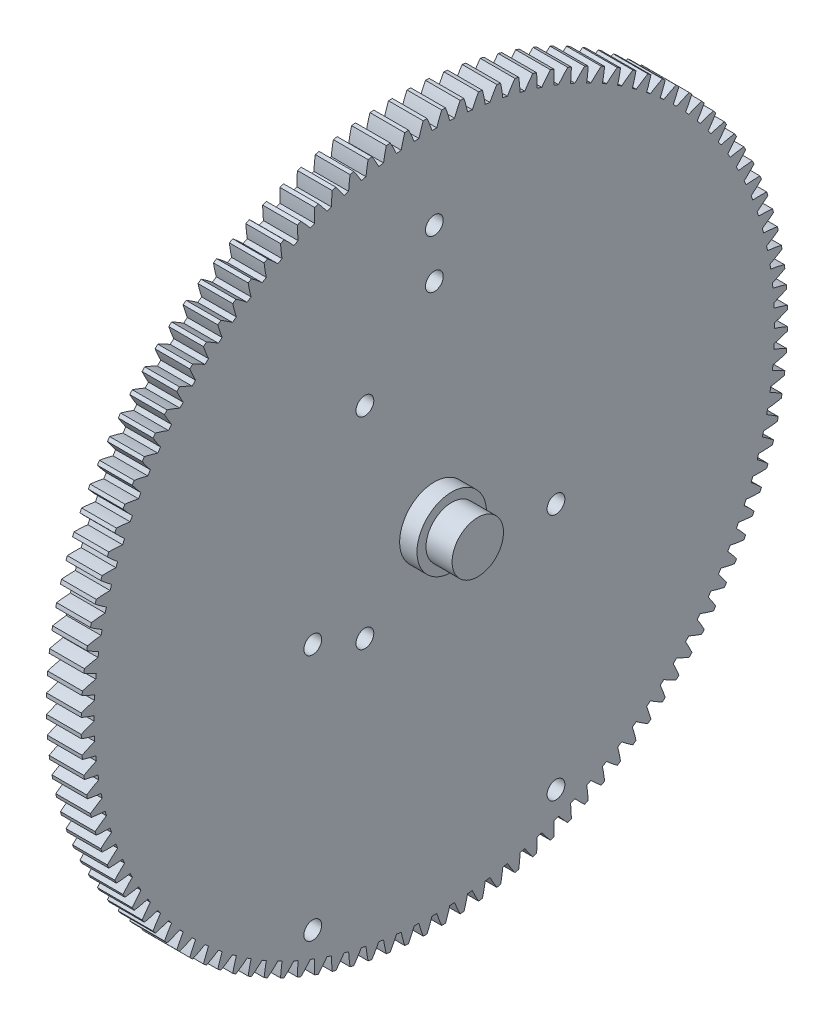
SolidWorks part; units mm, degrees
ref_plane "Plane1" through (0, 0, 0) normal (0, 0, 1) x (1, 0, 0)
ref_plane "Plane2" through (0, 0, 0) normal (0, 1, 0) x (1, 0, 0)
ref_plane "Plane3" through (0, 0, 0) normal (1, 0, 0) x (0, 0, -1)
other "Configuration Table"
sketch "HoldingSke" plane through (0, 0, 0) normal (0, 1, 0) x (1, 0, 0)
  line L0 (0, 0) -> (-152.4, -263.9645)
  line L1 (-15, 0) -> (100, 0) construction
  line L2 (0, 0) -> (-2.1039, 2.3779)
  line L3 (0, 0) -> (-11.863, 4.5341)
  line L4 (0, 0) -> (-4.318, 7.479)
  line L5 (0, 0) -> (-47.5972, -17.7524)
  line L6 (0, 0) -> (-10.5278, -7.1032)
  line L7 (-2.1039, 2.3779) -> (8.8308, 51.9871)
  line L8 (-76.2, 54.61) -> (-54.9402, 54.61)
  line L9 (-71.009, 38.7566) -> (-53.1078, 45.2721)
  line L10 (-76.2, 71.12) -> (104.1128, 71.12)
  line L11 (0, 0) -> (-12.7, 0)
  line L12 (-76.2, 101.6) -> (-76.1147, 101.6)
  line L13 (24.9733, 27.94) -> (52.9518, 28.4284)
  line L14 (24.9733, 27.94) -> (24.9746, 27.94)
  line L15 (24.9733, 27.94) -> (100.4006, 29.5858)
  circle A0 centre (0, 0) radius 9.525
  circle A1 centre (0, 0) radius 38.1
  circle A2 centre (0, 0) radius 38.1
  circle A3 centre (0, 0) radius 9.525
  dimension "MHD" = 76.2
  dimension "Hub_dia" = 76.2
  dimension "Bore" = 19.05
  dimension "MBD" = 19.05
  dimension "Num_teeth" = 120
  dimension "Pitch" = 304.8
  dimension "Overall_len" = 50.8
  dimension "Show_teeth" = 120
  dimension "Thickness" = 12.7
  dimension "OAL" = 50.8001
  dimension "T_dim" = 21.2598
  dimension "Ap" = 20
  dimension "H" = 19.05
  dimension "Pitch_radius" = 180.3128
  dimension "Width" = 12.7
  dimension "Backlash" = 0.0853
  dimension "Addendum_fac" = 1
  dimension "Dedendum_fac" = 1.25
  dimension "Clearance_fac" = 0.25
  dimension "Dedendum_add" = 0.0013
sketch "BasProSke" plane through (0, 0, 0) normal (0, 1, 0) x (1, 0, 0)
  line L0 (-10, 0) -> (60, 0) construction
  line L1 (0, 0) -> (0, 129.1167)
  line L2 (0, 0) -> (12.7, 0)
  line L3 (12.7, 0) -> (12.7, 129.1167)
  line L4 (12.7, 129.1167) -> (0, 129.1167)
  dimension "Thickness" = 12.7
  dimension "Diameter" = 258.2333
revolve "Base-Revolve" add sketch "BasProSke" angle 360 about L0
sketch "TooCutSke" plane through (0, 0, 0) normal (1, 0, 0) x (0, 0, -1)
  line L1 (0, 0) -> (0, 107) construction
  line L2 (0, 0) -> (-1.8117, 126.9871) construction
  line L3 (0, 0) -> (-6.6485, 253.8949) construction
  line L4 (-1.8117, 126.9871) -> (-3.3242, 126.9475) construction
  arc A0 (0.878, 124.3498) -> (-0.878, 124.3498) centre (0, 0) ccw
  arc A1 (2.6872, 129.1141) -> (-2.6872, 129.1141) centre (0, 0) ccw
  circle A2 centre (0, 0) radius 127 construction
  circle A3 centre (0, 0) radius 119.341 construction
  arc A4 (-0.878, 124.3498) -> (-2.6872, 129.1141) centre (-49.2141, 108.7209) ccw
  arc A5 (2.6872, 129.1141) -> (0.878, 124.3498) centre (49.2141, 108.7209) ccw
  dimension "Root_dia" = 248.7058
  dimension "Overcut_dia" = 258.2841
  dimension "Pitch_dia" = 254
  dimension "Base_dia" = 238.6819
  dimension "Flank_rad" = 50.8
  dimension "Half_ang" = 1.5
  dimension "Half_CT" = 1.513
extrude "ToothCut" cut sketch "TooCutSke" along normal through all
fillet "Breaks" [suppressed] radius 0.0423
fillet "RootFillets" [suppressed] radius 0.5304
pattern_circular "TeethCuts" count 120 every 3 about axis through (-10, 0, 0) along (1, 0, 0) of "ToothCut", "RootFillets", "Breaks"
sketch "HubNeaOneSke" plane through (0, 0, 0) normal (-1, 0, 0) x (0, 0, 1)
  circle A0 centre (0, 0) radius 38.1
  dimension "Diameter" = 76.2
extrude "HubNearOne" [suppressed] add sketch "HubNeaOneSke" along normal blind 38.1001
sketch "HubNeaBotSke" plane through (0, 0, 0) normal (-1, 0, 0) x (0, 0, 1)
  circle A0 centre (0, 0) radius 38.1
  dimension "Diameter" = 76.2
extrude "HubNearBoth" [suppressed] add sketch "HubNeaBotSke" along normal blind 19.05
ref_plane "FarPln" through (12.7, 0, 0) normal (1, 0, 0) x (0, 0, -1)
sketch "HubFarSke" plane through (12.7, 0, 0) normal (1, 0, 0) x (0, 0, -1)
  circle A0 centre (0, 0) radius 38.1
  dimension "Diameter" = 76.2
extrude "HubFar" [suppressed] add sketch "HubFarSke" along normal blind 19.05
sketch "BorSke" plane through (0, 0, 0) normal (1, 0, 0) x (0, 0, -1)
  circle A0 centre (0, 0) radius 9.525
  dimension "Diameter" = 19.05
extrude "Bore" [suppressed] cut sketch "BorSke" along normal mid plane 101.6001
sketch "KeySke" plane through (0, 0, 0) normal (1, 0, 0) x (0, 0, -1)
  line L0 (-2.3813, 0) -> (-2.3813, 11.7348)
  line L1 (-2.3813, 11.7348) -> (2.3813, 11.7348)
  line L2 (2.3813, 11.7348) -> (2.3813, 0)
  line L3 (0, 0) -> (0, 34) construction
  line L4 (-2.3813, 0) -> (2.3813, 0)
  dimension "Offset" = 11.7348
  dimension "Width" = 4.7625
extrude "Keyway" [suppressed] cut sketch "KeySke" along normal mid plane 101.6001
pattern_circular "Keyway2" [suppressed] count 2 every 90 about axis through (-10, 0, 0) along (1, 0, 0)
sketch "Sketch1" plane through (0, 0, 0) normal (-1, 0, 0) x (0, 0, 1)
  line L0 (0, 12.7) -> (44.585, 12.7) construction
  line L1 (0, 12.7) -> (0, -76.4863) construction
  circle A2 centre (25.4, 49.53) radius 3.2512
  circle A3 centre (25.4, -24.13) radius 3.2512
  circle A4 centre (0, 93.98) radius 3.2512
  circle A5 centre (0, 76.2) radius 3.2512
  circle A6 centre (44.45, -16.51) radius 3.2512
  circle A7 centre (44.45, -106.934) radius 3.2512
  circle A8 centre (-44.45, -106.934) radius 3.2512
  circle A9 centre (-44.45, -16.51) radius 3.2512
  point P9 (0, 0)
  dimension "D1" = 6.5024
  dimension "D2" = 6.5024
  dimension "D6" = 6.5024
  dimension "D7" = 6.5024
  dimension "D10" = 6.5024
  dimension "D11" = 6.5024
  dimension "D3" = 17.78
  dimension "D4" = 73.66
  dimension "D5" = 25.4
  dimension "D8" = 76.2
  dimension "D9" = 73.66
  dimension "D12" = 90.424
  dimension "D13" = 44.45
  dimension "D14" = 16.51
  dimension "D15" = 12.7
extrude "Cut-Extrude1" cut sketch "Sketch1" against normal through all
sketch "Sketch2" plane through (12.7, 0, 0) normal (1, 0, 0) x (0, 0, -1)
  circle A0 centre (0, 0) radius 12.7
  dimension "D1" = 25.4
extrude "Boss-Extrude1" add sketch "Sketch2" along normal blind 6.35
sketch "Sketch3" plane through (19.05, 0, 0) normal (1, 0, 0) x (0, 0, -1)
  circle A0 centre (0, 0) radius 9.398
  dimension "D1" = 18.796
extrude "Boss-Extrude2" add sketch "Sketch3" along normal blind 9.525
equation "' \"Pitch@HoldingSke\" = 4"
equation "' \"Num_teeth@HoldingSke\" = 12"
equation "' \"Ap@HoldingSke\" =  20"
equation "' \"Ap@HoldingSke\" = 20"
equation "' \"Width@HoldingSke\" = 0.5"
equation "' \"Hub_dia@HoldingSke\"= 1"
equation "' \"Hub_dia@HoldingSke\" = 1"
equation "' \"Overall_len@HoldingSke\" = 1.0"
equation "' \"Bore@HoldingSke\" = 0.75"
equation "' \"T_dim@HoldingSke\" = 0.85"
equation "' \"Width@KeySke\" = 0.25"
equation "' \"Show_teeth@HoldingSke\" = 13"
equation "' \"Backlash@HoldingSke\" = 0.009"
equation "' \"Addendum_fac@HoldingSke\" = 1.0"
equation "' \"Dedendum_fac@HoldingSke\" = 1.25"
equation "' \"Dedendum_add@HoldingSke\" = 0.00005"
equation "' \"Clearance_fac@HoldingSke\" = 0.25"
equation "' \"Pitch@HoldingSke\" = 0.5"
equation "' \"Num_teeth@HoldingSke\" = 23"
equation "' \"Show_teeth@HoldingSke\" = 23"
equation "' \"Backlash@HoldingSke\" = 0.0375"
equation "\"Overcut_dia@TooCutSke\" = (\"Num_teeth@HoldingSke\" + 2 * \"Addendum_fac@HoldingSke\") / \"Pitch@HoldingSke\" + 0.002"
equation "\"Pitch_dia@TooCutSke\" = \"Num_teeth@HoldingSke\" / \"Pitch@HoldingSke\""
equation "\"Base_dia@TooCutSke\" = \"Num_teeth@HoldingSke\" / \"Pitch@HoldingSke\" * cos((\"Ap@HoldingSke\"  * 3.14159265 / 180))"
equation "\"Root_dia@TooCutSke\" = (\"Num_teeth@HoldingSke\" + 2) / \"Pitch@HoldingSke\" - 2 * (\"Addendum_fac@HoldingSke\" + \"Dedendum_fac@HoldingSke\") / \"Pitch@HoldingSke\" - \"Dedendum_add@HoldingSke\" * 2"
equation "\"Half_ang@TooCutSke\" = 180 / \"Num_teeth@HoldingSke\""
equation "\"Half_CT@TooCutSke\" = \"Num_teeth@HoldingSke\" / \"Pitch@HoldingSke\" * sin((3.14159265 / 2 / \"Num_teeth@HoldingSke\")) / 2 - 7 * \"Backlash@HoldingSke\" / 4"
equation "\"Flank_rad@TooCutSke\" = \"Num_teeth@HoldingSke\" / \"Pitch@HoldingSke\" / 5"
equation "\"Radius@RootFillets\" = \"Clearance_fac@HoldingSke\" / \"Pitch@HoldingSke\" + \"Dedendum_add@HoldingSke\""
equation "\"Break_rad@Breaks\" = 0.02 / \"Pitch@HoldingSke\""
equation "\"Thickness@HoldingSke\" = \"Width@HoldingSke\""
equation "\"OAL@HoldingSke\" = \"Thickness@HoldingSke\""
equation "\"MHD@HoldingSke\" = (\"Num_teeth@HoldingSke\" + 2) / \"Pitch@HoldingSke\" - 2 * (\"Addendum_fac@HoldingSke\" + \"Dedendum_fac@HoldingSke\")  / \"Pitch@HoldingSke\" - \"Dedendum_add@HoldingSke\" * 2"
equation "\"MBD@HoldingSke\" = (\"Num_teeth@HoldingSke\" + 2) / \"Pitch@HoldingSke\" - 2 * (\"Addendum_fac@HoldingSke\" + \"Dedendum_fac@HoldingSke\")  / \"Pitch@HoldingSke\" - \"Dedendum_add@HoldingSke\" * 2 - 0.002"
equation "\"MHD@HoldingSke\" = ((sgn( \"MHD@HoldingSke\" - \"Hub_dia@HoldingSke\" )-1)*( \"MHD@HoldingSke\" - \"Hub_dia@HoldingSke\" ))/-2+ \"Hub_dia@HoldingSke\""
equation "\"MBD@HoldingSke\" = ((sgn( \"MBD@HoldingSke\" - \"Bore@HoldingSke\" )-1)*( \"MBD@HoldingSke\" - \"Bore@HoldingSke\" ))/-2+ \"Bore@HoldingSke\""
equation "\"OAL@HoldingSke\" = ((sgn( \"OAL@HoldingSke\" - \"Overall_len@HoldingSke\" )+1)*( \"OAL@HoldingSke\" - \"Overall_len@HoldingSke\" ))/2 + \"Overall_len@HoldingSke\" + 0.000002"
equation "\"Num_teeth@TeethCuts\" = int( \"Show_teeth@HoldingSke\" ) + 1"
equation "\"Num_teeth@TeethCuts\" = ((sgn( \"Num_teeth@TeethCuts\" - \"Num_teeth@HoldingSke\" )-1)*( \"Num_teeth@TeethCuts\" - \"Num_teeth@HoldingSke\" ))/-2+ \"Num_teeth@HoldingSke\""
equation "\"Num_teeth@TeethCuts\" = ((sgn( \"Num_teeth@TeethCuts\" - 2.0)+1)*( \"Num_teeth@TeethCuts\" - 2.0))/2 +2.0"
equation "\"Angle@TeethCuts\" = 360.0 / \"Num_teeth@HoldingSke\""
equation "\"Diameter@BasProSke\" = (\"Num_teeth@HoldingSke\" + 2 * \"Addendum_fac@HoldingSke\") / \"Pitch@HoldingSke\""
equation "\"Thickness@BasProSke\"  = \"Thickness@HoldingSke\""
equation "' \"Fillet_rad@BasProSke\" =  \"Thickness@HoldingSke\" * 0.05"
equation "' \"Fillet_rad@BasProSke\" = \"Thickness@HoldingSke\" * 0.05"
equation "\"MHD@HoldingSke\" = ((sgn( \"MHD@HoldingSke\" - \"Root_dia@TooCutSke\" )-1)*( \"MHD@HoldingSke\" - \"Root_dia@TooCutSke\" ))/-2+ \"Root_dia@TooCutSke\""
equation "\"Diameter@HubNeaOneSke\" = \"MHD@HoldingSke\""
equation "\"Length@HubNearOne\" = \"OAL@HoldingSke\" - \"Thickness@BasProSke\""
equation "\"Diameter@HubNeaBotSke\" = \"MHD@HoldingSke\""
equation "\"Length@HubNearBoth\" = ( \"OAL@HoldingSke\" - \"Thickness@BasProSke\" ) / 2.0"
equation "\"Thickness@FarPln\" = \"Thickness@BasProSke\""
equation "\"Diameter@HubFarSke\" = \"MHD@HoldingSke\""
equation "\"Length@HubFar\" = ( \"OAL@HoldingSke\" - \"Thickness@BasProSke\" ) / 2.0"
equation "\"Diameter@BorSke\" = \"MBD@HoldingSke\""
equation "\"D1@Bore\" = \"OAL@HoldingSke\" * 2.0"
equation "\"D1@Keyway\" = \"OAL@HoldingSke\" * 2.0"
equation "\"Offset@KeySke\" = \"T_dim@HoldingSke\" - \"MBD@HoldingSke\" / 2.0"
